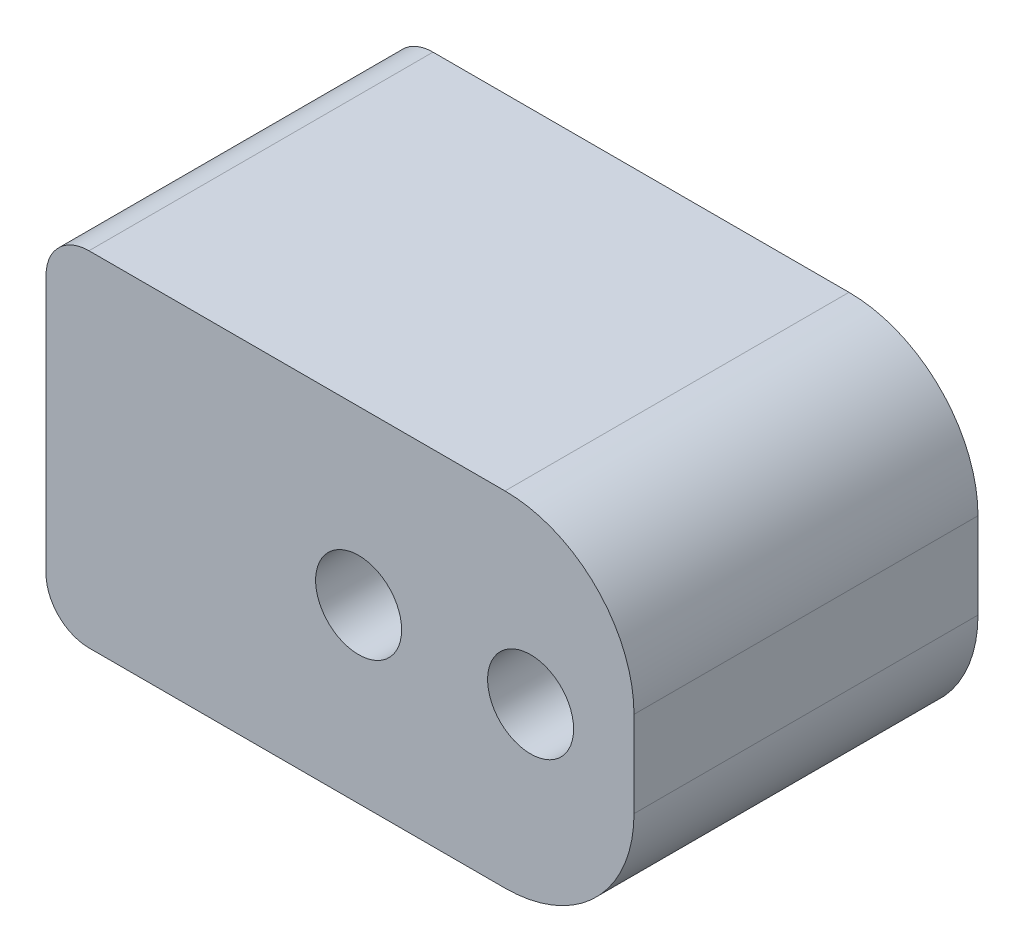
SolidWorks part; units mm, degrees
ref_plane "Front" through (0, 0, 0) normal (0, 0, 1) x (1, 0, 0)
ref_plane "Top" through (0, 0, 0) normal (0, 1, 0) x (1, 0, 0)
ref_plane "Right" through (0, 0, 0) normal (1, 0, 0) x (0, 0, -1)
sketch "Sketch1" plane through (0, 0, 0) normal (0, 0, 1) x (1, 0, 0)
  line L0 (-7.27, 4) -> (0, 4)
  line L1 (0, -4) -> (-7.27, -4)
  line L2 (-7.27, 4) -> (-7.27, -4)
  line L3 (55, 0) -> (-55, 0) construction
  line L4 (0, 4) -> (6.4045, 4)
  line L5 (0, 4) -> (0, -4)
  line L6 (0, -4) -> (6.4045, -4)
  line L7 (6.4045, 4) -> (6.4045, -4)
  circle A0 centre (0, 0) radius 4
  circle A1 centre (0, 0) radius 1
  circle A2 centre (4, 0) radius 1
  dimension "D1" = 8
  dimension "D3" = 2
  dimension "D4" = 4
  dimension "D2" = 7.27
extrude "Boss-Extrude1" add sketch "Sketch1" along normal blind 8 contours A0 L0 L2 L1 | A1 L5 A0 | A1 L5 A0 | A0 A2 L6 L7 L4 region at (-5.1093, 0, 0) region at (1.6632, 0, 0) region at (-1.7825, 0, 0) region at (3.2023, 3.8975, 0)
sketch "Sketch4" plane through (-7.27, 0, 0) normal (-1, 0, 0) x (0, 0, 1)
  line L0 (55, 0) -> (-55, 0) construction
  circle A0 centre (4, 0) radius 3.25
  dimension "D1" = 6.5
extrude "Cut-Extrude3" cut sketch "Sketch4" against normal blind 2.7 from offset 0.4 offset against normal yes
ref_plane "Plane1" through (0, 0, 4) normal (0, 0, 1) x (1, 0, 0)
sketch "Sketch3" plane through (0, 0, 4) normal (0, 0, 1) x (1, 0, 0)
  line L0 (4.4, 0) -> (-4.4, 0) construction
  circle A0 centre (-5, 0) radius 3.25
  circle A1 centre (0, 0) radius 1 construction
  dimension "D1" = 6.5
  dimension "D2" = 5
extrude "Cut-Extrude2" [suppressed] cut sketch "Sketch3" against normal mid plane 2.3
fillet "Fillet2" radius 1 2 edges at (-7.27, -4, 4) (-7.27, 4, 4)
fillet "Fillet3" radius 3 2 edges at (6.4045, -4, 4) (6.4045, 4, 4)
